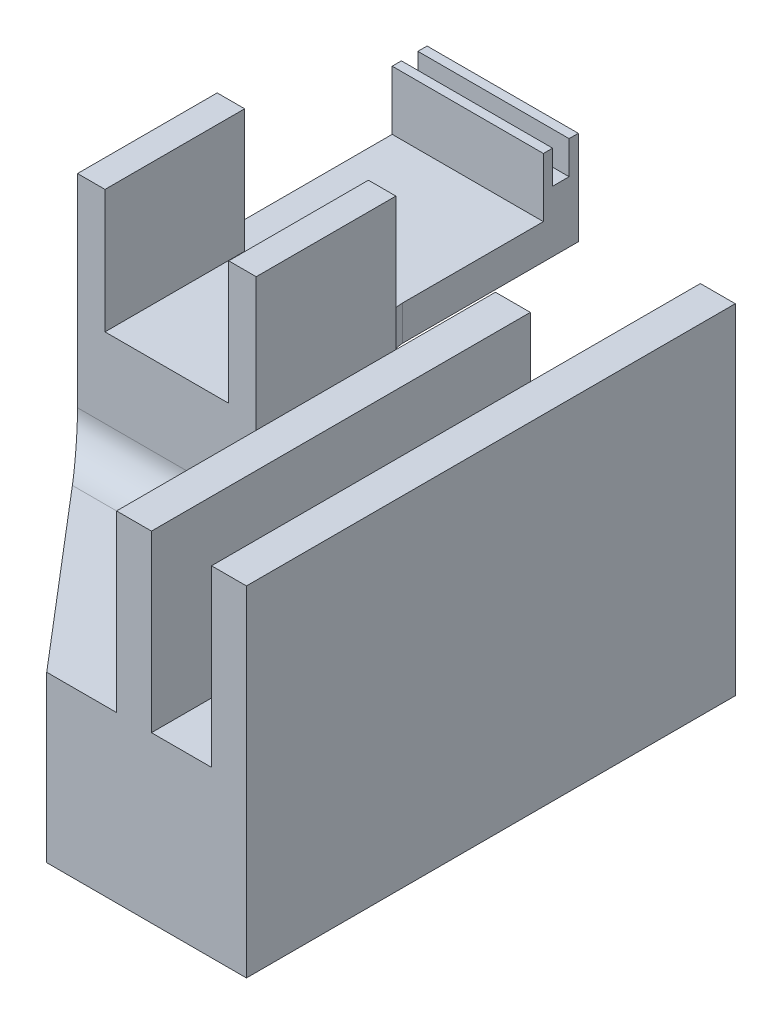
SolidWorks part; units mm, degrees
ref_plane "Front Plane" through (0, 0, 0) normal (0, 0, 1) x (1, 0, 0)
ref_plane "Top Plane" through (0, 0, 0) normal (0, 1, 0) x (1, 0, 0)
ref_plane "Right Plane" through (0, 0, 0) normal (1, 0, 0) x (0, 0, -1)
sketch "Sketch2" plane through (0, 0, 0) normal (0, 0, 1) x (1, 0, 0)
  line L0 (-11.25, 7.44) -> (-11.25, -15)
  line L1 (-11.25, -15) -> (11.25, -15)
  line L2 (11.25, -15) -> (11.25, 7.44)
  line L3 (11.25, 7.44) -> (16.25, 7.44)
  line L4 (16.25, 7.44) -> (16.25, -65.8)
  line L5 (16.25, -65.8) -> (-16.25, -65.8)
  line L6 (-16.25, -65.8) -> (-16.25, 7.44)
  line L7 (-16.25, 7.44) -> (-11.25, 7.44)
  line L8 (0, -15) -> (0, 0) construction
  point P11 (-12.5, 9.5755)
  dimension "D1" = 22.5
  dimension "D2" = 5
  dimension "D3" = 50.8
  dimension "D4" = 22.44
  dimension "D5" = 15
extrude "Boss-Extrude1" add sketch "Sketch2" along normal mid plane 25.4
sketch "Sketch4" plane through (0, 0, 0) normal (1, 0, 0) x (0, 0, -1)
  line L0 (12.7, -15) -> (44.525, -15)
  line L2 (44.525, -15) -> (44.525, -4.2628)
  line L3 (44.525, -4.2628) -> (50.875, -4.2628)
  line L4 (50.875, -4.2628) -> (50.875, -21.35)
  line L5 (50.875, -21.35) -> (12.7, -21.35)
  line L6 (12.7, -15) -> (12.7, -21.35)
  line L7 (12.7, -65.8) -> (12.7, 7.44) construction
  point P2 (12.7, -15.0938)
  point P9 (-12.7, -15.7239)
  point P11 (12.7, -15.8587)
  point P13 (47.7, -4.2628)
  dimension "D1" = 35
  dimension "D2" = 6.35
  dimension "D3" = 6.35
  dimension "D4" = 17.0872
extrude "Boss-Extrude2" add sketch "Sketch4" along normal up to surface and the other way up to surface up to face at (11.25, -3.78, 0) other way up to face at (-16.25, -29.18, 0)
sketch "Sketch5" plane through (0, -4.2628, 0) normal (0, 1, 0) x (1, 0, 0)
  line L0 (-16.25, 44.525) -> (-16.25, 50.875) construction
  line L1 (-16.25, 49.2) -> (11.25, 49.2)
  line L2 (-16.25, 49.2) -> (-16.25, 46.2)
  line L3 (-16.25, 46.2) -> (11.25, 46.2)
  line L4 (11.25, 49.2) -> (11.25, 46.2)
  line L5 (11.25, 50.875) -> (11.25, 44.525) construction
  point P8 (11.25, 47.7)
  point P9 (11.25, 47.7)
  dimension "D1" = 3
extrude "Cut-Extrude1" cut sketch "Sketch5" against normal blind 6
fillet "Fillet2" radius 6.35 1 edges at (11.25, -18.175, -12.7)
fillet "Fillet3" radius 6.35 1 edges at (0, -21.35, -12.7)
sketch "Sketch6" plane through (0, 0, 12.7) normal (0, 0, 1) x (1, 0, 0)
  line L0 (16.25, -65.8) -> (52.572, -65.8)
  line L1 (52.572, -65.8) -> (52.572, -4.05)
  line L2 (52.572, -4.05) -> (46.222, -4.05)
  line L3 (46.222, -4.05) -> (46.222, -35.8)
  line L4 (46.222, -35.8) -> (35.3, -35.8)
  line L5 (35.3, -35.8) -> (35.3, -4.05)
  line L6 (35.3, -4.05) -> (28.95, -4.05)
  line L7 (28.95, -4.05) -> (28.95, -35.8)
  line L8 (28.95, -35.8) -> (16.25, -35.8)
  line L9 (16.25, -65.8) -> (16.25, 7.44) construction
  line L10 (16.25, -35.8) -> (16.25, -65.8)
  dimension "D1" = 30
  dimension "D2" = 31.75
  dimension "D3" = 10.922
  dimension "D4" = 12.7
  dimension "D5" = 6.35
extrude "Boss-Extrude3" add sketch "Sketch6" against normal blind 50.8 and the other way blind 38.1
sketch "Sketch7" plane through (28.95, 0, 0) normal (-1, 0, 0) x (0, 0, 1)
  line L1 (-38.1, -4.05) -> (-18.1, -4.05)
  line L2 (-38.1, -4.05) -> (-38.1, -35.8)
  line L3 (-38.1, -35.8) -> (-18.1, -35.8)
  line L4 (-18.1, -4.05) -> (-18.1, -35.8)
  dimension "D1" = 20
extrude "Cut-Extrude2" cut sketch "Sketch7" against normal up to next
fillet "Fillet4" radius 12.7 1 edges at (16.25, -50.8, -12.7)
sketch "Sketch8" plane through (0, -65.8, 0) normal (0, -1, 0) x (1, 0, 0)
  line L0 (-16.25, 12.7) -> (16.25, 50.8)
  line L1 (16.25, 50.8) -> (16.25, 12.7)
  line L2 (16.25, 12.7) -> (-16.25, 12.7)
extrude "Boss-Extrude4" add sketch "Sketch8" against normal up to surface (30 mm away) up to face at (25.6979, -35.8, 4.6109)
fillet "Fillet6" radius 6.35 1 edges at (0, -35.8, 12.7)
